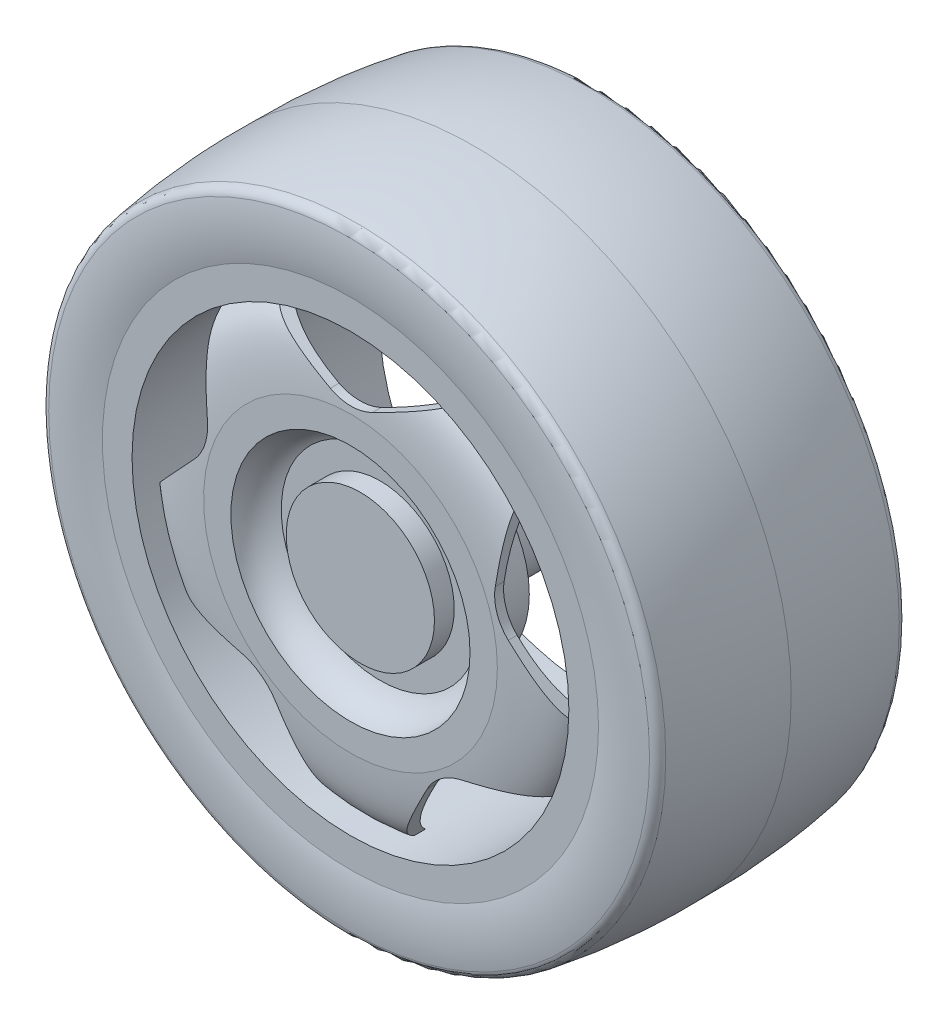
SolidWorks part; units mm, degrees
ref_plane "Front Plane" through (0, 0, 0) normal (0, 0, 1) x (1, 0, 0)
ref_plane "Top Plane" through (0, 0, 0) normal (0, 1, 0) x (1, 0, 0)
ref_plane "Right Plane" through (0, 0, 0) normal (1, 0, 0) x (0, 0, -1)
sketch "Sketch1" plane through (0, 0, 0) normal (1, 0, 0) x (0, 0, -1)
  line L0 (-0.0107, 12.1) -> (-0.0107, 14.8643)
  line L1 (-0.0107, 25.1) -> (24.9893, 25.1)
  line L2 (-0.0107, 22.1) -> (2.9893, 22.1)
  line L3 (2.9893, 10) -> (2.9893, 7.5)
  line L4 (2.9893, 7.5) -> (0.9893, 7.5)
  line L5 (0.9893, 7.5) -> (0.9893, 0)
  line L6 (-13.2759, 0) -> (14.215, 0) construction
  line L7 (-0.0107, 22.1) -> (-0.0107, 25.1)
  line L8 (24.9893, 25.1) -> (24.9893, 22.1)
  line L9 (24.9893, 22.1) -> (4.0868, 22.1)
  line L10 (0.9893, 14.8643) -> (0.9893, 12.992)
  line L11 (4.0868, 10) -> (8.0868, 10)
  line L12 (8.0868, 10) -> (8.0868, 0)
  line L13 (8.0868, 0) -> (0.9893, 0)
  arc A0 (-0.0107, 12.1) -> (2.9893, 10) centre (-0.3983, 8.3534) cw
  arc A1 (4.0868, 22.1) -> (0.9893, 14.8643) centre (9.2266, 15.6189) ccw
  arc A2 (0.9893, 12.992) -> (4.0868, 10) centre (-0.1123, 8.7522) cw
  spline S0 degree 3 poles (2.9893, 22.1) (1.2339, 21.0874) (0.2751, 20.019) (-0.0107, 14.8643) knots 0 0 0 0 1 1 1 1
  point P6 (3, 12)
  dimension "D5" = 2.2559
  dimension "D2" = 25
  dimension "D3" = 3
  dimension "D4" = 3
  dimension "D6" = 2
  dimension "D7" = 2.5
  dimension "D8" = 2
  dimension "D9" = 13
  dimension "D10" = 1
  dimension "D11" = 1
  dimension "D12" = 4
revolve "Revolve1" add sketch "Sketch1" angle 360 about L6
sketch "Sketch2" plane through (0, 0, 0.0107) normal (0, 0, 1) x (1, 0, 0)
  line L0 (0, 22.1) -> (0, 0) construction
  line L1 (-10, 19.7081) -> (-2.1298, 16.0027)
  line L2 (2.1298, 16.0027) -> (10, 19.7081)
  line L3 (15.6534, 15.6007) -> (14.5614, 6.9707)
  line L4 (15.8777, 2.9195) -> (21.8337, -3.4204)
  line L5 (19.6743, -10.0664) -> (11.1292, -11.6946)
  line L6 (7.6831, -14.1984) -> (3.494, -21.8221)
  line L7 (-3.494, -21.8221) -> (-7.6831, -14.1984)
  line L8 (-11.1292, -11.6946) -> (-19.6743, -10.0664)
  line L9 (-21.8337, -3.4204) -> (-15.8777, 2.9195)
  line L10 (-14.5614, 6.9707) -> (-15.6534, 15.6007)
  circle A0 centre (0, 0) radius 22.1 construction
  circle A1 centre (0, 0) radius 22.1 construction
  arc A2 (-2.1298, 16.0027) -> (2.1298, 16.0027) centre (0, 20.5264) ccw
  arc A3 (10, 19.7081) -> (-10, 19.7081) centre (0, 0) ccw
  arc A4 (14.5614, 6.9707) -> (15.8777, 2.9195) centre (19.5218, 6.343) ccw
  arc A5 (21.8337, -3.4204) -> (15.6534, 15.6007) centre (0, 0) ccw
  arc A6 (11.1292, -11.6946) -> (7.6831, -14.1984) centre (12.0651, -16.6062) ccw
  arc A7 (3.494, -21.8221) -> (19.6743, -10.0664) centre (0, 0) ccw
  arc A8 (-7.6831, -14.1984) -> (-11.1292, -11.6946) centre (-12.0651, -16.6062) ccw
  arc A9 (-19.6743, -10.0664) -> (-3.494, -21.8221) centre (0, 0) ccw
  arc A10 (-15.8777, 2.9195) -> (-14.5614, 6.9707) centre (-19.5218, 6.343) ccw
  arc A11 (-15.6534, 15.6007) -> (-21.8337, -3.4204) centre (0, 0) ccw
  point P12 (0, 15)
  point P35 (0, 0)
  dimension "D3" = 5
  dimension "D1" = 10
  dimension "D2" = 15
  dimension "D4" = 5
extrude "Cut-Extrude1" cut sketch "Sketch2" against normal blind 10
sketch "Sketch3" plane through (0, 0, -8.0868) normal (0, 0, -1) x (-1, 0, 0)
  circle A0 centre (0, 0) radius 6
  dimension "D1" = 12
extrude "Boss-Extrude1" add sketch "Sketch3" along normal blind 25
sketch "Sketch4" plane through (0, 0, -33.0868) normal (0, 0, -1) x (-1, 0, 0)
  line L0 (-2.5475, 2.4) -> (2.5475, 2.4)
  line L1 (-3.5, 0) -> (3.5, 0) construction
  line L2 (-2.5475, -2.4) -> (2.5475, -2.4)
  arc A0 (-2.5475, 2.4) -> (-2.5475, -2.4) centre (0, 0) ccw
  arc A1 (2.5475, -2.4) -> (2.5475, 2.4) centre (0, 0) ccw
  dimension "D1" = 7
  dimension "D2" = 2.4
extrude "Cut-Extrude2" cut sketch "Sketch4" against normal blind 12
sketch "Sketch5" plane through (0, 0, 0) normal (1, 0, 0) x (0, 0, -1)
  line L0 (-0.0107, 25.1) -> (24.9893, 25.1)
  line L1 (-0.0107, 25.1) -> (-0.0107, -25.1) construction
  line L2 (24.9893, -25.1) -> (24.9893, 25.1) construction
  line L3 (12.4893, 32.1) -> (12.4893, 25.1) construction
  line L4 (0, 0) -> (33.0868, 0) construction
  line L5 (33.0868, -2.4) -> (33.0868, 2.4) construction
  arc A0 (12.4893, 32.1) -> (0.6752, 31.2185) centre (11.3986, -32.8908) ccw
  arc A1 (-0.1463, 30.3962) -> (-0.0107, 25.1) centre (13.6641, 28.1) ccw
  arc A2 (-0.1463, 30.3962) -> (0.6752, 31.2185) centre (0.8401, 30.2322) cw
  arc A3 (25.1249, 30.3962) -> (24.9893, 25.1) centre (11.3145, 28.1) cw
  arc A4 (25.1249, 30.3962) -> (24.3034, 31.2185) centre (24.1384, 30.2322) ccw
  arc A5 (12.4893, 32.1) -> (24.3034, 31.2185) centre (13.58, -32.8908) cw
  point P6 (12.4893, 32.1)
  point P7 (-0.0107, 31.1)
  point P8 (12.4893, 31.1)
  point P21 (-0.0107, 31.1)
  dimension "D3" = 65
  dimension "D4" = 14
  dimension "D5" = 1
  dimension "D1" = 7
  dimension "D2" = 6
revolve "Revolve2" add sketch "Sketch5" angle 360 about L4
